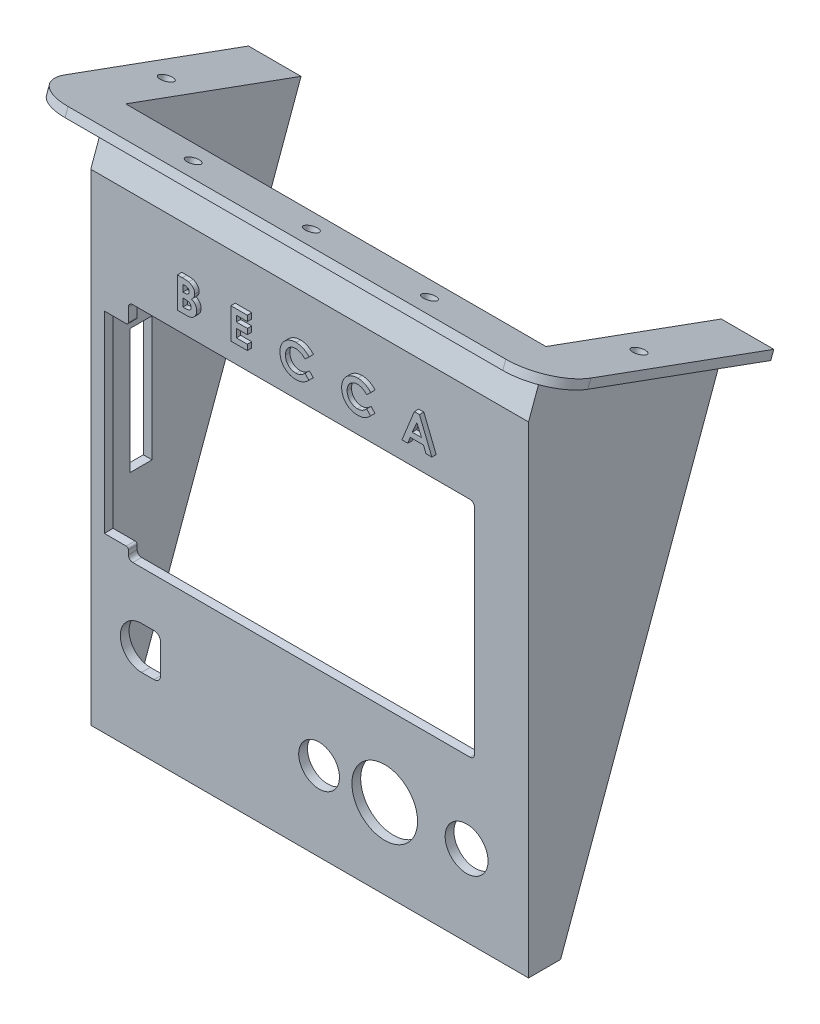
SolidWorks part; units mm, degrees
ref_plane "Front Plane" through (0, 0, 0) normal (0, 0, 1) x (1, 0, 0)
ref_plane "Top Plane" through (0, 0, 0) normal (0, 1, 0) x (1, 0, 0)
ref_plane "Right Plane" through (0, 0, 0) normal (1, 0, 0) x (0, 0, -1)
sketch "Sketch1" plane through (0, 0, 0) normal (0, 0, 1) x (1, 0, 0)
  line L0 (-37.4, 25.5) -> (-37.4, 21)
  line L1 (-37.4, -25.5) -> (41.65, -25.5)
  line L2 (-42.9, -23) -> (-42.9, 21)
  line L3 (-37.4, 25.5) -> (41.65, 25.5)
  line L4 (41.65, -25.5) -> (41.65, 25.5)
  line L7 (-37.4, 21) -> (-42.9, 21)
  line L8 (-42.9, -23) -> (-37.4, -23)
  line L9 (-37.4, -23) -> (-37.4, -25.5)
  line L10 (-1000, 0) -> (49000, 0) construction
  line L12 (-46, -62.5) -> (54, -62.5)
  line L13 (-46, -62.5) -> (-46, 47.5)
  line L14 (-46, 47.5) -> (54, 47.5)
  line L15 (54, -62.5) -> (54, 47.5)
  point P0 (0, 0)
  point P13 (41.65, 0)
  point P15 (0, 0)
  dimension "D2" = 51
  dimension "D3" = 5.5
  dimension "D4" = 4.5
  dimension "D5" = 2.5
  dimension "D6" = 41.65
  dimension "D7" = 47.5
  dimension "D8" = 100
  dimension "D9" = 110
  dimension "D10" = 54
  dimension "D11" = 42.9
extrude "Boss-Extrude1" add sketch "Sketch1" along normal blind 2
sketch "Sketch2" plane through (54, 0, 0) normal (1, 0, 0) x (0, 0, -1)
  line L1 (0, -62.5) -> (0, 47.5) construction
  line L2 (0, 47.5) -> (3.979, 58.4322)
  line L3 (44.0308, 43.8546) -> (3.979, 58.4322)
  line L4 (0, -62.5) -> (0, 47.5)
  line L6 (5.3209, -62.5) -> (44.0308, 43.8546)
  line L7 (0, -62.5) -> (5.3209, -62.5)
  dimension "D1" = 113.1801
  dimension "D2" = 42.6222
  dimension "D3" = 11.6338
  dimension "D4" = 110
extrude "Boss-Extrude2" add sketch "Sketch2" against normal blind 2
sketch "Sketch3" plane through (54, 0, 0) normal (1, 0, 0) x (0, 0, -1)
  line L0 (-2, 47.5) -> (2.213, 59.075)
  line L1 (2.213, 59.075) -> (3.979, 58.4322)
  line L2 (-2, 47.5) -> (0, 47.5) construction
  line L3 (3.979, 58.4322) -> (0, 47.5) construction
  line L4 (-2, 47.5) -> (0, 47.5)
  line L5 (3.979, 58.4322) -> (0, 47.5)
  line L6 (44.0308, 43.8546) -> (3.979, 58.4322) construction
extrude "Boss-Extrude4" add sketch "Sketch3" against normal through all
fillet "Fillet1" radius 1 4 edges at (-37.4, -25.5, 1) (41.65, -25.5, 1) (41.65, 25.5, 1) (-37.4, 25.5, 1)
fillet "Fillet2" radius 0.5 2 edges at (-37.4, -23, 1) (-37.4, 21, 1)
sketch "Sketch4" plane through (-46, 0, 0) normal (-1, 0, 0) x (0, 0, 1)
  line L0 (2, 47.5) -> (2, -62.5) construction
  line L1 (2, -62.5) -> (0, -62.5) construction
  line L3 (-44.0308, 43.8546) -> (-3.979, 58.4322) construction
  line L4 (-3.979, 58.4322) -> (-2.213, 59.075) construction
  line L5 (-2.213, 59.075) -> (2, 47.5) construction
  line L6 (2, 47.5) -> (2, -62.5)
  line L7 (2, -62.5) -> (0, -62.5)
  line L9 (-44.0308, 43.8546) -> (-3.979, 58.4322)
  line L10 (-3.979, 58.4322) -> (-2.213, 59.075)
  line L11 (-2.213, 59.075) -> (2, 47.5)
  line L17 (-5.3209, -62.5) -> (0, -62.5)
  line L18 (0, -62.5) -> (0, 47.5)
  line L19 (0, 47.5) -> (-3.979, 58.4322)
  line L20 (-3.979, 58.4322) -> (-44.0308, 43.8546)
  line L21 (-44.0308, 43.8546) -> (-5.3209, -62.5)
  line L25 (-3.979, 58.4322) -> (-44.0308, 43.8546)
  line L26 (-44.0308, 43.8546) -> (-5.3209, -62.5)
  line L27 (-5.3209, -62.5) -> (0, -62.5)
  line M1 (0, 47.5) -> (0, -62.5)
  line M6 (-3.979, 58.4322) -> (0, 47.5)
  dimension "D1" = 0
extrude "Boss-Extrude5" add sketch "Sketch4" against normal blind 2 contours L9 L26 M1 M6 region at (-46, 9.4893, -14.9583)
sketch "Sketch6" plane through (0, 0, 2) normal (0, 0, 1) x (1, 0, 0)
  line L3 (54, -62.5) -> (54, 47.5) construction
  line L4 (-31.55, -36.55) -> (-34.4, -36.55)
  line L5 (-31.05, -44.75) -> (-31.05, -38.05) construction
  line L6 (-31.55, -37.55) -> (-34.4, -37.55) construction
  line L8 (-34.4, -45.25) -> (-31.55, -45.25) construction
  line L9 (-31.55, -37.55) -> (-34.4, -37.55) construction
  line L10 (-31.05, -44.75) -> (-31.05, -38.05) construction
  line L11 (-34.4, -45.25) -> (-31.55, -45.25) construction
  line L12 (-34.4, -46.25) -> (-31.55, -46.25)
  line L13 (-30.05, -44.75) -> (-30.05, -38.05)
  circle A4 centre (21.15, -44.2) radius 7.5
  arc A7 (-34.4, -37.55) -> (-34.4, -45.25) centre (-34.4, -41.4) ccw construction
  circle A9 centre (6.15, -44.4) radius 1.65 construction
  circle A10 centre (6.15, -44.4) radius 1.65 construction
  circle A11 centre (6.15, -44.4) radius 4.65
  arc A12 (-31.05, -38.05) -> (-31.55, -37.55) centre (-31.55, -38.05) ccw construction
  arc A13 (-31.55, -45.25) -> (-31.05, -44.75) centre (-31.55, -44.75) ccw construction
  arc A14 (-34.4, -37.55) -> (-34.4, -45.25) centre (-34.4, -41.4) ccw construction
  arc A15 (-31.05, -38.05) -> (-31.55, -37.55) centre (-31.55, -38.05) ccw construction
  arc A16 (-31.55, -45.25) -> (-31.05, -44.75) centre (-31.55, -44.75) ccw construction
  arc A17 (-34.4, -36.55) -> (-34.4, -46.25) centre (-34.4, -41.4) ccw
  arc A18 (-31.55, -46.25) -> (-30.05, -44.75) centre (-31.55, -44.75) ccw
  arc A19 (-30.05, -38.05) -> (-31.55, -36.55) centre (-31.55, -38.05) ccw
  arc A20 (43.7178, -43.5) -> (43.7178, -44.5) centre (39.85, -44) ccw construction
  arc A21 (43.7178, -43.5) -> (43.7178, -44.5) centre (39.85, -44) ccw construction
  arc A22 (43.7178, -43.5) -> (43.7178, -44.5) centre (39.85, -44) cw construction
  arc A23 (44.7096, -43.3718) -> (44.7096, -44.6282) centre (39.85, -44) ccw
  arc A24 (44.7096, -43.3718) -> (44.7096, -44.6282) centre (39.85, -44) cw
  point P14 (39.85, -51.3669)
  dimension "D2" = 14.15
  dimension "D3" = 15
  dimension "D1" = 1
  dimension "D4" = 1
  dimension "D7" = 3
extrude "Cut-Extrude1" cut sketch "Sketch6" against normal up to next
sketch "Sketch7" plane through (-46, 0, 0) normal (-1, 0, 0) x (0, 0, 1)
  line L0 (-9, -14) -> (-9, 12.5) construction
  line L1 (-10, 13.5) -> (-5, 13.5)
  line L2 (-10, 13.5) -> (-10, -15)
  line L3 (-10, -15) -> (-5, -15)
  line L4 (-5, 13.5) -> (-5, -15)
  line L5 (-6, 34.5) -> (-6, -52.7) construction
  line L6 (-9, 12.5) -> (-6, 12.5) construction
  line L7 (-9, -14) -> (-6, -14) construction
  dimension "D1" = 1
  dimension "D2" = 1
  dimension "D3" = 1
  dimension "D4" = 1
extrude "Cut-Extrude2" cut sketch "Sketch7" against normal up to next
sketch "Sketch10" plane through (54, 0, 0) normal (1, 0, 0) x (0, 0, -1)
  line L1 (-2, -62.5) -> (5.3209, -62.5)
  line L2 (-2, -62.5) -> (-2, -60.5)
  line L3 (-2, -60.5) -> (5.3209, -60.5)
  line L4 (5.3209, -62.5) -> (5.3209, -60.5)
  line L9 (-2, -62.5) -> (5.3209, -62.5)
  line L10 (5.3209, -62.5) -> (44.0308, 43.8546)
  line L11 (44.0308, 43.8546) -> (2.213, 59.075)
  line L12 (2.213, 59.075) -> (-2, 47.5)
  line L13 (-2, 47.5) -> (-2, -62.5)
  line L14 (-2, -62.5) -> (5.3209, -62.5)
  line L15 (5.3209, -62.5) -> (44.0308, 43.8546) construction
  line M8 (-2, -62.5) -> (5.3209, -62.5)
  line M12 (-2, 47.5) -> (-2, -62.5)
  dimension "D2" = 2
  dimension "D1" = 0
extrude "Boss-Extrude7" add sketch "Sketch10" against normal through all contours L4 L3 M8 M12 region at (54, -61.5, -1.6604)
sketch "Sketch11" plane through (0, 52.8758, -19.2452) normal (0, 0.9397, -0.342) x (1, 0, 0)
  line L0 (-56, 26.3763) -> (-56, -28.1253)
  line L1 (-56, -28.1253) -> (64, -28.1253)
  line L2 (64, -28.1253) -> (64, 26.3763)
  line L3 (-46, 26.3763) -> (-56, 26.3763)
  line L4 (54, 26.3763) -> (64, 26.3763)
  line L8 (54, -18.1253) -> (54, 26.3763)
  line L9 (54, 26.3763) -> (52, 26.3763)
  line L10 (52, 26.3763) -> (52, -16.246)
  line L11 (52, -16.246) -> (-44, -16.246)
  line L12 (-44, -16.246) -> (-44, 26.3763)
  line L13 (-44, 26.3763) -> (-46, 26.3763)
  line L14 (-46, 26.3763) -> (-46, -18.1253)
  line L15 (-46, -18.1253) -> (54, -18.1253)
  line L16 (54, -18.1253) -> (54, 26.3763)
  line L22 (-46, 26.3763) -> (-46, -18.1253)
  line L23 (-46, -18.1253) -> (54, -18.1253)
  dimension "D1" = 0
  dimension "D2" = 10
extrude "Boss-Extrude8" add sketch "Sketch11" against normal blind 2
fillet "Fillet4" radius 10 2 edges at (-56, 61.5555, 7.526) (64, 61.5555, 7.526)
sketch "Sketch12" plane through (0, 52.8758, -19.2452) normal (0, 0.9397, -0.342) x (1, 0, 0)
  line L0 (-952.9782, -22.1856) -> (49047.0218, -22.1856) construction
  line L1 (-56, 18.0259) -> (64, 18.0259) construction
  line L2 (52, -16.246) -> (-44, -16.246) construction
  line L3 (-46, -28.1253) -> (54, -28.1253) construction
  line L4 (20.1389, -16.246) -> (20.1389, -28.1253) construction
  line L5 (64, -18.1253) -> (64, 26.3763) construction
  line L6 (-56, 4.9645) -> (-44, 4.9645) construction
  line L7 (-56, 26.3763) -> (-56, -18.1253) construction
  line L8 (-44, 26.3763) -> (-44, -16.246) construction
  line L9 (-50, -995.0355) -> (-50, 49004.9645) construction
  line L10 (4, -1000) -> (4, 49000) construction
  line L11 (-50, -18.1851) -> (4, -18.1851) construction
  circle A0 centre (4, -22.1856) radius 1.5
  circle A1 centre (-23, -22.1856) radius 1.5
  circle A4 centre (-50, 0) radius 1.5
  circle A5 centre (31, -22.1856) radius 1.5
  circle A6 centre (58, 0) radius 1.5
  point P7 (4, 18.0259)
  point P18 (20.1389, -22.1856)
  point P22 (-50, 4.9645)
  point P32 (-23, -18.1851)
  dimension "D1" = 3
extrude "Cut-Extrude3" cut sketch "Sketch12" against normal up to next
sketch "Sketch13" plane through (0, 0, 2) normal (0, 0, 1) x (1, 0, 0)
  line L0 (-26.0121, 30.5) -> (26.0121, 30.5) construction
  line L1 (40.65, 25.5) -> (-36.4, 25.5) construction
  text T0 "<b>BECCA</b>" font "Century Gothic" height 7
  point P0 (0, 0)
  point P3 (0, 30.5)
  dimension "D1" = 5
extrude "Boss-Extrude9" add sketch "Sketch13" along normal blind 1
